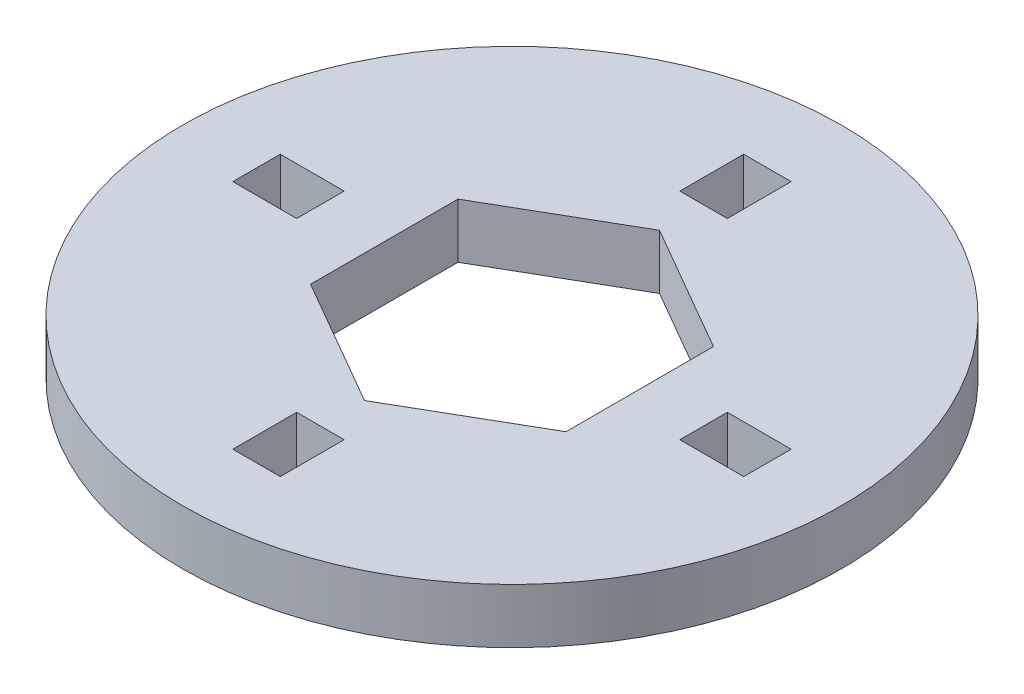
SolidWorks part; units mm, degrees
ref_plane "Front Plane" through (0, 0, 0) normal (0, 0, 1) x (1, 0, 0)
ref_plane "Top Plane" through (0, 0, 0) normal (0, 1, 0) x (1, 0, 0)
ref_plane "Right Plane" through (0, 0, 0) normal (1, 0, 0) x (0, 0, -1)
sketch "Sketch1" plane through (0, 0, 0) normal (0, 1, 0) x (1, 0, 0)
  line L4 (-10.5, -1.3) -> (-10.5, 1.3)
  line L5 (1.3, -10.5) -> (-1.3, -10.5)
  line L6 (1.3, -10.5) -> (1.3, -14)
  line L7 (1.3, -14) -> (-1.3, -14)
  line L8 (-1.3, -10.5) -> (-1.3, -14)
  line L9 (0, -14) -> (0, -10.5) construction
  line L10 (1.3, -12.25) -> (-1.3, -12.25) construction
  line L11 (-10.5, 1.3) -> (-14, 1.3)
  line L12 (-14, -1.3) -> (-14, 1.3)
  line L13 (-10.5, -1.3) -> (-14, -1.3)
  line L14 (-1.3, 10.5) -> (1.3, 10.5)
  line L15 (1.3, 10.5) -> (1.3, 14)
  line L16 (-1.3, 14) -> (1.3, 14)
  line L17 (-1.3, 10.5) -> (-1.3, 14)
  line L18 (10.5, 1.3) -> (10.5, -1.3)
  line L19 (10.5, -1.3) -> (14, -1.3)
  line L20 (14, 1.3) -> (14, -1.3)
  line L21 (10.5, 1.3) -> (14, 1.3)
  line L23 (0, -8.0829) -> (7, -4.0415)
  line L24 (7, -4.0415) -> (7, 4.0415)
  line L25 (7, 4.0415) -> (0, 8.0829)
  line L26 (0, 8.0829) -> (-7, 4.0415)
  line L27 (-7, 4.0415) -> (-7, -4.0415)
  line L28 (-7, -4.0415) -> (0, -8.0829)
  circle A0 centre (0, 0) radius 18.0624
  arc A1 (-18, -1.5) -> (-1.5, -18) centre (0, 0) ccw construction
  circle A2 centre (0, 0) radius 7 construction
  point P13 (0, -12.25)
  point P24 (0, 0)
  dimension "D2" = 14
  dimension "D1" = 4
extrude "Boss-Extrude1" add sketch "Sketch1" along normal blind 3
